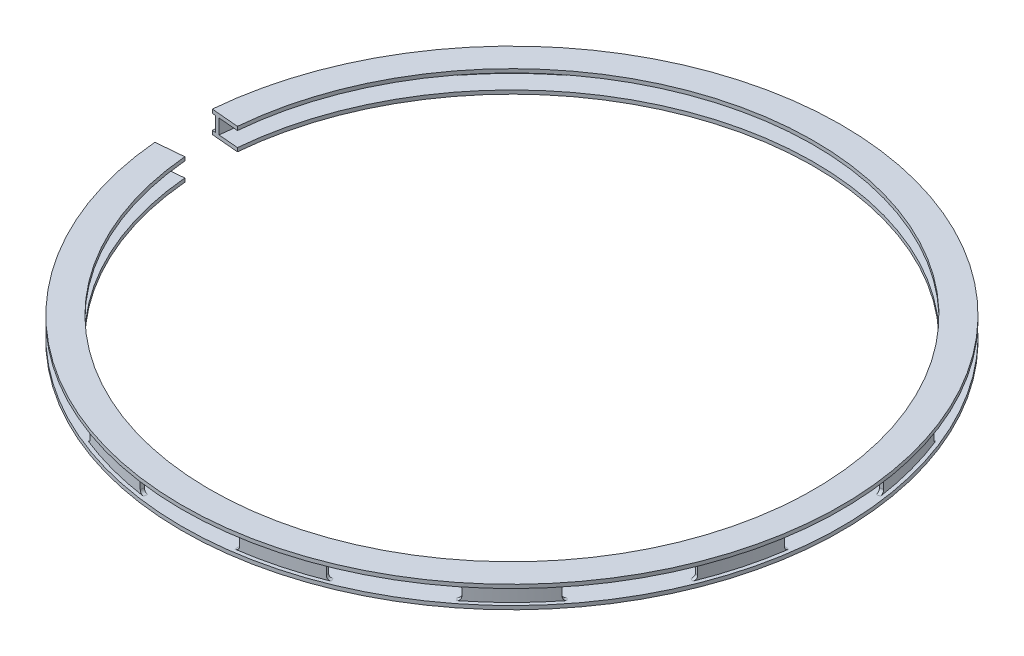
SolidWorks part; units mm, degrees
ref_plane "Front Plane" through (0, 0, 0) normal (0, 0, 1) x (1, 0, 0)
ref_plane "Top Plane" through (0, 0, 0) normal (0, 1, 0) x (1, 0, 0)
ref_plane "Right Plane" through (0, 0, 0) normal (1, 0, 0) x (0, 0, -1)
sketch "Sketch1" plane through (0, 0, 0) normal (0, 0, 1) x (1, 0, 0)
  line L0 (0, 0) -> (0, 7.484) construction
  line L1 (0, 0) -> (44.75, 0) construction
  line L2 (41, 3) -> (41, 2.5)
  line L3 (44.75, 0) -> (41, 0)
  line L4 (44.75, 0) -> (44.75, 3) construction
  line L5 (44.75, 3) -> (41, 3)
  line L6 (41, 0) -> (41, 3) construction
  line L7 (41, 2.5) -> (43.75, 2.5)
  line L8 (43.75, 2.5) -> (43.75, 0.5)
  line L9 (43.75, 0.5) -> (41, 0.5)
  line L10 (41, 0.5) -> (41, 0)
  line L11 (44.75, 2.5) -> (44.75, 3)
  line L12 (44.75, 2.5) -> (44.25, 2.5)
  line L13 (44.25, 2.5) -> (44.25, 0.5)
  line L14 (44.25, 0.5) -> (44.75, 0.5)
  line L15 (44.75, 0.5) -> (44.75, 0)
  dimension "D1" = 3.75
  dimension "D2" = 3
  dimension "D3" = 41
  dimension "D4" = 0.5
  dimension "D5" = 0.5
  dimension "D6" = 0.5
  dimension "D7" = 0.5
  dimension "D8" = 0.5
  dimension "D9" = 0.5
revolve "Revolve1" add sketch "Sketch1" angle 350 mid plane about L0
sketch "Sketch2" plane through (0, 0, 0) normal (0, 0, 1) x (1, 0, 0)
  line L0 (44.75, 0.5) -> (-44.5797, 0.5) construction
  line L1 (44.25, 2.5) -> (43.25, 2.5)
  line L2 (44.25, 2.5) -> (44.25, 0.5)
  line L3 (44.25, 0.5) -> (43.25, 0.5)
  line L4 (43.25, 2.5) -> (43.25, 0.5)
  line L5 (0, 0) -> (0, 19.9129) construction
  dimension "D1" = 1
revolve "Cut-Revolve1" cut sketch "Sketch2" angle 17.5 mid plane about L5
fillet "Fillet1" radius 0.5 4 edges at (43.4879, 2.5, 6.6934) (43.4879, 0.5, 6.6934) (43.4879, 0.5, -6.6934) (43.4879, 2.5, -6.6934)
pattern_circular "CirPattern1" count 12 over 360 about axis through (0, 0.5, 0) along (0, -1, 0) skipping 6 of "Cut-Revolve1", "Fillet1"
